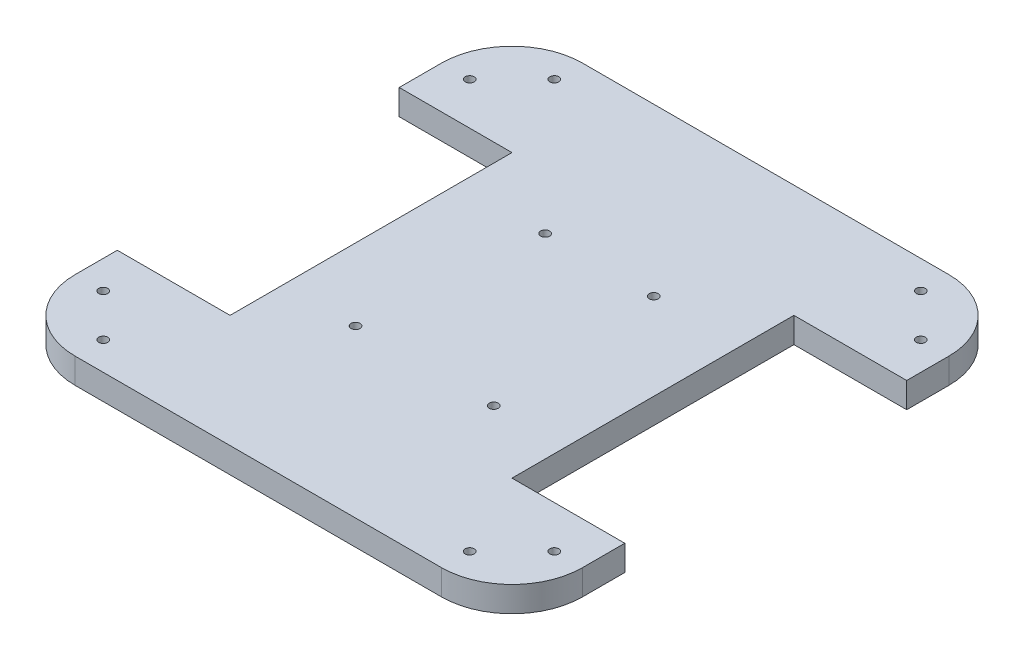
SolidWorks part; units mm, degrees
ref_plane "Front Plane" through (0, 0, 0) normal (0, 0, 1) x (1, 0, 0)
ref_plane "Top Plane" through (0, 0, 0) normal (0, 1, 0) x (1, 0, 0)
ref_plane "Right Plane" through (0, 0, 0) normal (1, 0, 0) x (0, 0, -1)
sketch "Sketch1" plane through (0, 0, 0) normal (0, 1, 0) x (1, 0, 0)
  line L1 (-65, -90) -> (65, -90)
  line L2 (-90, -65) -> (-90, 65)
  line L3 (-65, 90) -> (65, 90)
  line L4 (90, -65) -> (90, 65)
  arc A0 (-90, 65) -> (-65, 90) centre (-65, 65) cw
  arc A1 (65, 90) -> (90, 65) centre (65, 65) cw
  arc A2 (90, -65) -> (65, -90) centre (65, -65) cw
  arc A3 (-65, -90) -> (-90, -65) centre (-65, -65) cw
  point P4 (-90, 0)
  point P6 (0, 90)
  dimension "D3" = 25
  dimension "D1" = 180
  dimension "D2" = 180
extrude "Plate" add sketch "Sketch1" along normal blind 9
sketch "Sketch3" plane through (0, 9, 0) normal (0, 1, 0) x (1, 0, 0)
  line L0 (-65, 90) -> (-65, -90) construction
  line L1 (65, 90) -> (65, -90) construction
  line L2 (-90, 65) -> (90, 65) construction
  line L3 (-90, -65) -> (90, -65) construction
  circle A0 centre (-65, 80) radius 1.6
  circle A1 centre (-80, 65) radius 1.6
  circle A2 centre (80, 65) radius 1.6
  circle A3 centre (80, -65) radius 1.6
  circle A4 centre (65, 80) radius 1.6
  circle A5 centre (65, -80) radius 1.6
  circle A6 centre (-65, -80) radius 1.6
  circle A7 centre (-80, -65) radius 1.6
  dimension "D1" = 3.2
  dimension "D2" = 15
  dimension "D3" = 15
  dimension "D4" = 15
  dimension "D5" = 15
  dimension "D6" = 15
  dimension "D7" = 15
  dimension "D8" = 15
  dimension "D9" = 15
extrude "Hex Holes" cut sketch "Sketch3" against normal through all
sketch "Sketch4" plane through (0, 9, 0) normal (0, 1, 0) x (1, 0, 0)
  line L0 (-90, -65) -> (-90, 65) construction
  line L1 (-65, -90) -> (65, -90) construction
  circle A0 centre (-24.5, -31) radius 1.6
  circle A1 centre (24.5, -31) radius 1.6
  circle A2 centre (-19.25, 31) radius 1.6
  circle A3 centre (19.25, 31) radius 1.6
  dimension "D1" = 3.2
  dimension "D2" = 62
  dimension "D3" = 49
  dimension "D4" = 5.25
  dimension "D5" = 38.5
  dimension "D6" = 65.5
  dimension "D7" = 59
extrude "Arduino Holes" cut sketch "Sketch4" against normal through all
sketch "Sketch5" plane through (0, 9, 0) normal (0, 1, 0) x (1, 0, 0)
  line L0 (-90, -65) -> (-90, 65) construction
  line L1 (-90, -50) -> (-50, -50)
  line L2 (-90, -50) -> (-90, 50)
  line L3 (-90, 50) -> (-50, 50)
  line L4 (-50, -50) -> (-50, 50)
  line L5 (90, -65) -> (90, 65) construction
  line L6 (90, -50) -> (50, -50)
  line L7 (90, -50) -> (90, 50)
  line L8 (90, 50) -> (50, 50)
  line L9 (50, -50) -> (50, 50)
  line L10 (-90, 0) -> (90, 0) construction
  point P14 (-90, 0)
  point P15 (90, 0)
  dimension "D1" = 100
  dimension "D3" = 40
extrude "Cut-Extrude1" cut sketch "Sketch5" against normal through all
